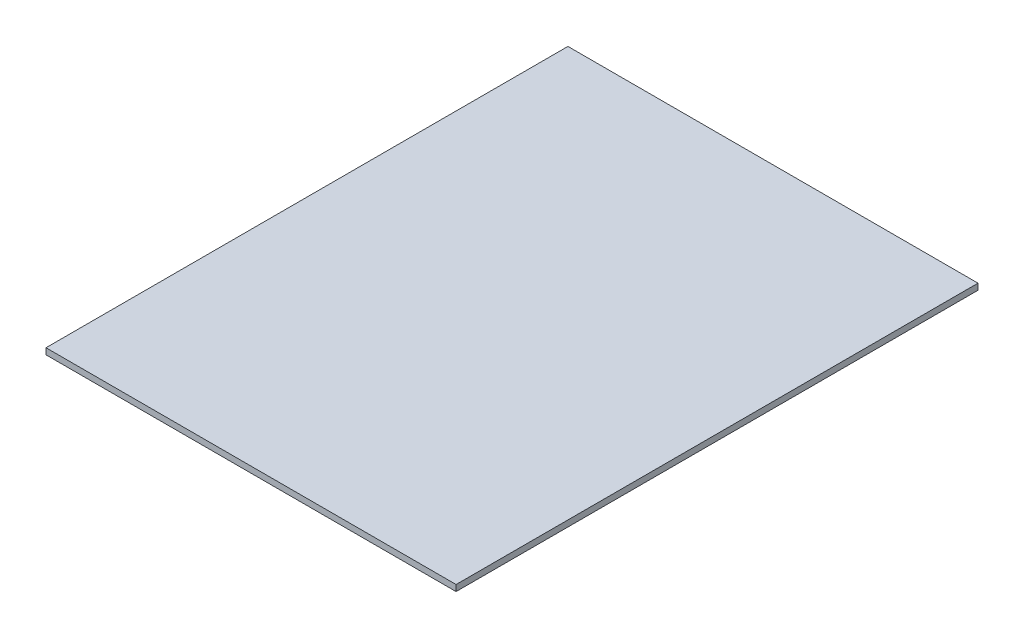
SolidWorks part; units mm, degrees
ref_plane "Front Plane" through (0, 0, 0) normal (0, 0, 1) x (1, 0, 0)
ref_plane "Top Plane" through (0, 0, 0) normal (0, 1, 0) x (1, 0, 0)
ref_plane "Right Plane" through (0, 0, 0) normal (1, 0, 0) x (0, 0, -1)
sketch "Sketch1" plane through (0, 0, 0) normal (0, 1, 0) x (1, 0, 0)
  line L1 (-55, -70) -> (55, -70)
  line L2 (-55, -70) -> (-55, 70)
  line L3 (-55, 70) -> (55, 70)
  line L4 (55, -70) -> (55, 70)
  line L5 (-55, -70) -> (55, 70) construction
  line L6 (-55, 70) -> (55, -70) construction
  point P0 (0, 0)
  dimension "D1" = 110
  dimension "D2" = 140
extrude "Boss-Extrude1" add sketch "Sketch1" along normal blind 1.65
